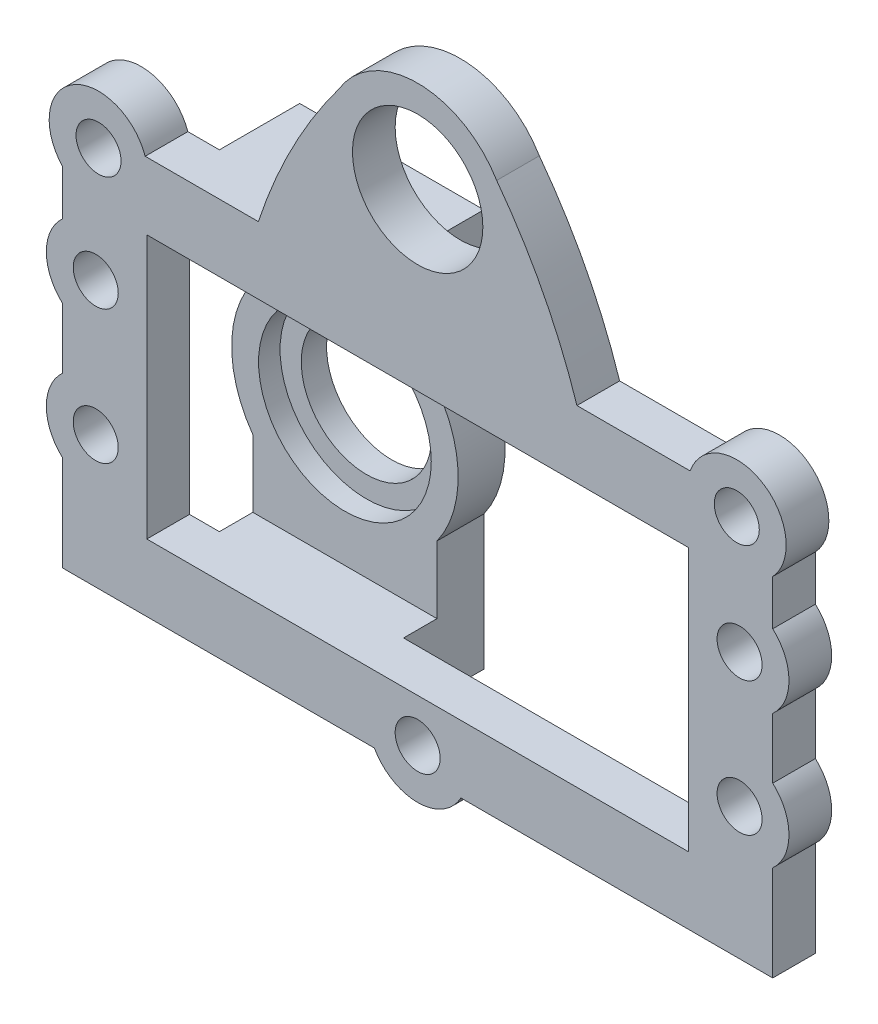
SolidWorks part; units mm, degrees
ref_plane "Front Plane" through (0, 0, 0) normal (0, 0, 1) x (1, 0, 0)
ref_plane "Top Plane" through (0, 0, 0) normal (0, 1, 0) x (1, 0, 0)
ref_plane "Right Plane" through (0, 0, 0) normal (1, 0, 0) x (0, 0, -1)
sketch "Sketch1" plane through (0, 0, 0) normal (0, 0, 1) x (1, 0, 0)
  line L1 (-26.416, -9.8) -> (26.416, -9.8)
  line L2 (-26.416, -9.8) -> (-26.416, 9.8)
  line L3 (-26.416, 9.8) -> (26.416, 9.8)
  line L4 (26.416, -9.8) -> (26.416, 9.8)
  line L5 (-26.416, -9.8) -> (26.416, 9.8) construction
  line L6 (-26.416, 9.8) -> (26.416, -9.8) construction
  line L7 (-20.15, -9.8) -> (20.15, -9.8)
  line L8 (-20.15, -9.8) -> (-20.15, 9.8)
  line L9 (-20.15, 9.8) -> (20.15, 9.8)
  line L10 (20.15, -9.8) -> (20.15, 9.8)
  line L11 (-20.15, -9.8) -> (20.15, 9.8) construction
  line L12 (-20.15, 9.8) -> (20.15, -9.8) construction
  line L13 (-26.416, 9.8) -> (26.416, 9.8)
  line L14 (-26.416, 9.8) -> (-26.416, 14.8)
  line L15 (-26.416, 14.8) -> (26.416, 14.8)
  line L16 (26.416, 9.8) -> (26.416, 14.8)
  line L17 (26.416, -9.8) -> (-26.416, -9.8)
  line L18 (26.416, -9.8) -> (26.416, -14.8)
  line L19 (26.416, -14.8) -> (-26.416, -14.8)
  line L20 (-26.416, -9.8) -> (-26.416, -14.8)
  circle A0 centre (-23.95, -4.974) radius 1.675
  circle A1 centre (-23.95, 4.974) radius 1.675
  circle A2 centre (23.95, 4.974) radius 1.675
  circle A3 centre (23.95, -4.974) radius 1.675
  point P0 (0, 0)
  point P14 (0, 0)
  dimension "D1" = 3.35
  dimension "D2" = 3.35
  dimension "D3" = 3.35
  dimension "D4" = 3.35
  dimension "D7" = 4.826
  dimension "D8" = 3.8
  dimension "D9" = 3.8
  dimension "D10" = 4.826
  dimension "D11" = 4.826
  dimension "D12" = 4.826
  dimension "D13" = 3.8
  dimension "D5" = 19.6
  dimension "D6" = 52.832
  dimension "D15" = 40.3
  dimension "D16" = 5
  dimension "D17" = 5
  dimension "3.9" = 3.8
extrude "Boss-Extrude2" add sketch "Sketch1" along normal blind 3.175 contours L1 L8 L3 L2 A1 A0 | L10 L1 L4 L3 A3 A2 | L14 L13 L16 L15 | L18 L17 L20 L19 region at (-23.1712, 0, 0) region at (23.1712, 0, 0)
sketch "Sketch3" plane through (0, 0, 0) normal (0, 0, -1) x (-1, 0, 0)
  line L3 (26.416, -14.8) -> (26.416, 14.8) construction
  line L4 (-26.416, -14.8) -> (26.416, -14.8) construction
  circle A0 centre (11.076, 0.11) radius 4.85
  circle A1 centre (11.076, 0.11) radius 6.85
  dimension "D1" = 15.34
  dimension "D2" = 14.91
  dimension "D4" = 9.7
  dimension "D3" = 2
extrude "Boss-Extrude3" add sketch "Sketch3" along normal blind 5.975 separate body
sketch "Sketch5" plane through (0, 0, 0) normal (0, 0, 1) x (1, 0, 0)
  circle A0 centre (-11.076, 0.11) radius 6.85
extrude "Cut-Extrude2" cut sketch "Sketch5" against normal blind 2.4892
sketch "Sketch14" plane through (0, 0, -5.975) normal (0, 0, -1) x (-1, 0, 0)
  line L0 (26.416, 14.8) -> (-26.416, 14.8) construction
  line L2 (4.226, 0.11) -> (4.226, 14.8)
  line L3 (4.226, 14.8) -> (16.926, 14.8)
  line L5 (-26.416, -14.8) -> (26.416, -14.8) construction
  line L8 (16.926, -14.8) -> (4.226, -14.8)
  line L9 (4.226, 0.11) -> (4.226, -14.8)
  line L10 (17.926, 0.11) -> (17.926, 3.6104)
  line L12 (16.926, 14.8) -> (17.926, 14.8)
  line L14 (16.926, -14.8) -> (17.926, -14.8)
  line L15 (17.926, 14.8) -> (17.926, -14.8)
  circle A0 centre (11.076, 0.11) radius 6.85 construction
  circle A1 centre (11.076, 0.11) radius 4.85
  circle M1 centre (11.076, 0.11) radius 6.85
extrude "Boss-Extrude4" add sketch "Sketch14" against normal up to surface (3.4858 mm away) contours L15 L12 L3 L2 L10 M1 | L15 L9 L8 L14 M1 region at (-11.076, -9.9123, -5.975) region at (-11.076, 10.0195, -5.975) up to face at (-6.226, 0.11, -2.4892)
sketch "Sketch15" plane through (0, 0, -5.975) normal (0, 0, -1) x (-1, 0, 0)
  line L0 (17.926, 14.8) -> (17.926, -14.8) construction
  line L1 (4.226, 14.8) -> (17.926, 14.8)
  line L2 (4.226, 14.8) -> (4.226, 9.8)
  line L3 (4.226, 9.8) -> (17.926, 9.8)
  line L4 (17.926, 14.8) -> (17.926, 9.8)
  line L5 (20.15, 9.8) -> (-20.15, 9.8) construction
  line L6 (4.226, -14.8) -> (4.226, 14.8) construction
  line L7 (17.926, -14.8) -> (4.226, -14.8)
  line L8 (17.926, -14.8) -> (17.926, -9.8)
  line L9 (17.926, -9.8) -> (4.226, -9.8)
  line L10 (4.226, -14.8) -> (4.226, -9.8)
  line L11 (-20.15, -9.8) -> (20.15, -9.8) construction
extrude "Boss-Extrude6" add sketch "Sketch15" against normal up to surface (5.975 mm away) contours L2 L1 L4 L3 | L8 L7 L10 L9 up to face at (0, 0, 0)
sketch "Sketch16" plane through (0, 0, 0) normal (0, 0, -1) x (-1, 0, 0)
  line L0 (-26.416, -14.8) -> (-26.416, 14.8) construction
  line L1 (4.226, 14.8) -> (-26.416, 14.8) construction
  circle A0 centre (-23.741, 13.587) radius 1.675
  dimension "D1" = 3.35
  dimension "D2" = 2.675
  dimension "D3" = 1.213
sketch "Sketch17" plane through (0, 0, 0) normal (0, 0, -1) x (-1, 0, 0)
  line L0 (26.416, 14.8) -> (17.926, 14.8) construction
  line L1 (26.416, -14.8) -> (26.416, 14.8) construction
  line L2 (-26.416, -14.8) -> (4.226, -14.8) construction
  circle A0 centre (23.741, 13.587) radius 1.675
  circle A1 centre (0, -13.025) radius 1.675
  dimension "D1" = 3.35
  dimension "D2" = 1.213
  dimension "D3" = 2.675
  dimension "D4" = 3.35
  dimension "D5" = 1.775
extrude "Cut-Extrude3" cut sketch "Sketch17" against normal blind 10 contours A1 | A0
extrude "Cut-Extrude4" cut sketch "Sketch16" against normal blind 10
sketch "Sketch18" plane through (0, 0, 0) normal (0, 0, -1) x (-1, 0, 0)
  line L0 (-1.7621, -9.8) -> (1.7621, -9.8)
  line L1 (-20.15, -9.8) -> (4.226, -9.8) construction
  circle A0 centre (-23.741, 13.587) radius 1.675
  circle A1 centre (23.741, 13.587) radius 1.675
  circle A2 centre (0, -13.025) radius 1.675
  circle A3 centre (0, -13.025) radius 3.675
  circle A4 centre (-23.741, 13.587) radius 3.675
  circle A5 centre (23.741, 13.587) radius 3.675
  circle M4 centre (0, -13.025) radius 1.675
  line M8 (4.226, -9.8) -> (-20.15, -9.8)
  line M14 (-26.416, -14.8) -> (4.226, -14.8)
  dimension "D1" = 2
extrude "Boss-Extrude7" add sketch "Sketch18" against normal up to surface (3.175 mm away) contours A3 M8 M14 M4 | A5 A1 | A3 M14 | A4 | A0 region at (0, -9.8889, 0) region at (0, -15.5798, 0) region at (-20.1699, 13.587, 0) up to face at (0, 6.678, 3.175)
sketch "Sketch20" plane through (0, 0, 0) normal (0, 0, -1) x (-1, 0, 0)
  circle A0 centre (-23.95, 4.974) radius 1.675
  circle A1 centre (-23.95, -4.974) radius 1.675
  circle A2 centre (23.95, -4.974) radius 1.675
  circle A3 centre (23.95, 4.974) radius 1.675
  circle A4 centre (23.95, 4.974) radius 3.675
  circle A5 centre (-23.95, 4.974) radius 3.675
  circle A6 centre (23.95, -4.974) radius 3.675
  circle A7 centre (-23.95, -4.974) radius 3.675
  dimension "D1" = 2
  dimension "D2" = 2
extrude "Boss-Extrude8" add sketch "Sketch20" against normal up to surface (3.175 mm away) up to face at (25.416, 13.587, 3.175)
sketch "Sketch23" plane through (0, 0, 0) normal (0, 0, -1) x (-1, 0, 0)
  line L0 (0, 0) -> (0, 4.1326)
  line L2 (4.226, 14.8) -> (-20.272, 14.8) construction
  line L3 (-6.85, 22.8) -> (-6.85, 14.8)
  line L4 (6.85, 22.8) -> (6.85, 14.8)
  line L5 (-6.85, 14.8) -> (6.85, 14.8)
  circle A0 centre (0, 22.8) radius 4.85
  circle A1 centre (0, 22.8) radius 6.85
  line M18 (4.226, 14.8) -> (-20.272, 14.8)
  dimension "D1" = 9.7
  dimension "D3" = 0
  dimension "D4" = 8
  dimension "D2" = 2
extrude "Boss-Extrude10" add sketch "Sketch23" against normal up to surface (3.175 mm away) contours A1 L3 L5 L4 M18 | A1 A0 region at (0, 15.7914, 0) region at (0, 29.4563, 0) up to face at (0, -0.1111, 3.175)
sketch "Sketch24" plane through (0, 0, 3.175) normal (0, 0, 1) x (1, 0, 0)
  line L0 (-6.85, 22.8) -> (0, 29.65)
  line L1 (0, 29.65) -> (-3.425, 26.225)
  line L2 (-3.425, 26.225) -> (-6.0639, 28.8639)
  line L3 (-6.85, 14.8) -> (-11.85, 14.8)
  line L4 (-20.272, 14.8) -> (-6.85, 14.8) construction
  line L5 (6.85, 14.8) -> (11.85, 14.8)
  line L6 (6.85, 22.8) -> (6.85, 14.8) construction
  line L7 (6.85, 14.8) -> (20.272, 14.8) construction
  line L8 (6.85, 22.8) -> (0, 29.65)
  line L9 (3.425, 26.225) -> (6.7095, 29.5095)
  arc A0 (6.85, 22.8) -> (-6.85, 22.8) centre (0, 22.8) ccw construction
  arc A1 (-4.8437, 27.6437) -> (-11.85, 14.8) centre (26.176, 2.3894) ccw
  arc A2 (4.8437, 27.6437) -> (11.85, 14.8) centre (-26.176, 2.3894) cw
  line M9 (20.272, 14.8) -> (6.85, 14.8)
  line M10 (6.85, 14.8) -> (6.85, 22.8)
  arc M11 (6.85, 22.8) -> (-6.85, 22.8) centre (0, 22.8) ccw
  line M12 (-6.85, 22.8) -> (-6.85, 14.8)
  line M13 (-6.85, 14.8) -> (-20.272, 14.8)
  dimension "D2" = 40
  dimension "D4" = 40
  dimension "D1" = 5
  dimension "D3" = 5
extrude "Boss-Extrude11" add sketch "Sketch24" against normal up to surface (3.175 mm away) contours A1 M11 M13 M12 | A2 M11 M10 M9 region at (-8.5897, 18.476, 3.175) region at (8.5897, 18.476, 3.175) up to face at (10.8888, 3.4427, 0)
sketch "Sketch21" plane through (0, 0, 0) normal (0, 0, -1) x (-1, 0, 0)
  line L0 (4.226, 14.8) -> (11.85, 14.8) construction
  line L1 (0, 14.8) -> (0, 17.0333)
  circle A0 centre (-7.5, 14.8) radius 1.675
  circle A1 centre (-7.5, 14.8) radius 3.675
  line M14 (4.226, 14.8) -> (11.85, 14.8)
  dimension "D1" = 7.5
  dimension "D2" = 3.35
  dimension "D3" = 2
extrude "Boss-Extrude9" add sketch "Sketch21" against normal up to surface (3.175 mm away) contours A1 A0 M14 region at (11.0711, 14.8, 0) up to face at (0, 4.2138, 3.175)
sketch "Sketch25" plane through (0, 0, -2.4892) normal (0, 0, 1) x (1, 0, 0)
  circle A0 centre (-11.076, 0.11) radius 6.425
  dimension "D1" = 12.85
extrude "Cut-Extrude5" cut sketch "Sketch25" against normal blind 1.6 contours A0
sketch "Sketch26" plane through (0, 0, -2.4892) normal (0, 0, 1) x (1, 0, 0)
  circle A0 centre (-11.076, 0.11) radius 6.425
  circle A1 centre (-11.076, 0.11) radius 8.425
  dimension "D1" = 2
extrude "Boss-Extrude12" add sketch "Sketch26" against normal up to surface (3.4858 mm away) contours A1 | A0 up to face at (-11.076, 0, -5.975)
